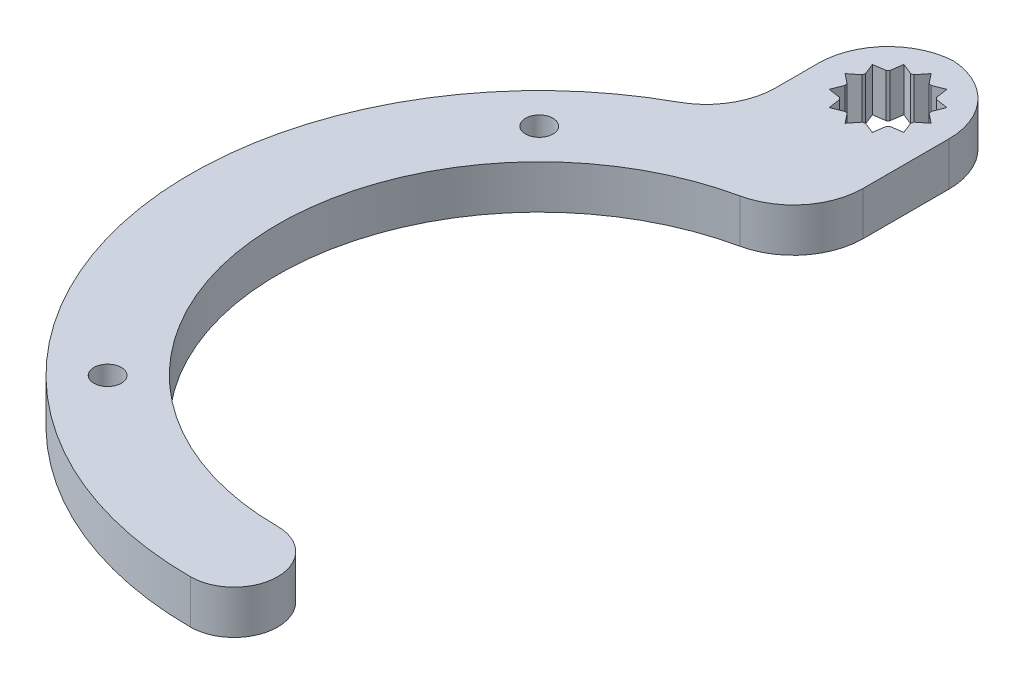
SolidWorks part; units mm, degrees
material "Pine"
ref_plane "Front Plane" through (0, 0, 0) normal (0, 0, 1) x (1, 0, 0)
ref_plane "Top Plane" through (0, 0, 0) normal (0, 1, 0) x (1, 0, 0)
ref_plane "Right Plane" through (0, 0, 0) normal (1, 0, 0) x (0, 0, -1)
sketch "Sketch1" plane through (0, 0, 0) normal (0, 1, 0) x (1, 0, 0)
  line L0 (0, 0) -> (19.05, 0)
  line L1 (19.05, 0) -> (19.05, -19.05)
  line L2 (0, 0) -> (0, -22.7571)
  line L3 (19.05, -19.05) -> (19.05, -120.65) construction
  line L4 (19.05, -31.75) -> (19.05, -19.05)
  line L5 (19.05, -9.525) -> (0, -9.525) construction
  line L6 (19.05, -69.85) -> (-12.3809, -38.4191) construction
  line L7 (19.05, -69.85) -> (-12.3809, -101.2809) construction
  arc A0 (19.05, -19.05) -> (19.05, -120.65) centre (19.05, -69.85) ccw
  arc A1 (19.05, -31.75) -> (19.05, -107.95) centre (19.05, -69.85) ccw
  arc A2 (19.05, -107.95) -> (19.05, -120.65) centre (19.05, -114.3) cw
  circle A3 centre (9.525, -9.525) radius 3
  circle A4 centre (19.05, -69.85) radius 44.45 construction
  circle A5 centre (-12.3809, -38.4191) radius 2
  circle A6 centre (-12.3809, -101.2809) radius 2
  dimension "D2" = 76.2
  dimension "D5" = 6
  dimension "D6" = 88.9
  dimension "D7" = 4
  dimension "D8" = 4
  dimension "D1" = 12.7
  dimension "D3" = 19.05
  dimension "D4" = 19.05
  dimension "D9" = 135
  dimension "D10" = 45
extrude "Boss-Extrude1" add sketch "Sketch1" along normal blind 6.35 contours L3 A1 L4 A0 | A0 L1 L0 L2 | A2 L3 region at (9.525, 0, 0.2968) region at (9.569, 0, 21.1296)
fillet "Fillet1" radius 10.16 4 edges at (0, 3.175, 22.7571) (19.05, 3.175, 31.75) (0, 3.175, 0) (19.05, 3.175, 0)
sketch "Sketch2" plane through (0, 6.35, 0) normal (0, 1, 0) x (1, 0, 0)
  line L0 (9.525, -4.525) -> (9.525, -3.255) construction
  line L1 (9.525, -3.255) -> (10.6293, -4.6485)
  line L2 (9.525, -3.255) -> (8.4207, -4.6485)
  line L3 (12.66, -4.095) -> (11.0069, -4.7496)
  line L4 (12.66, -4.095) -> (12.9196, -5.854)
  line L5 (12.025, -5.1949) -> (12.66, -4.095) construction
  line L6 (14.955, -6.39) -> (13.196, -6.1304)
  line L7 (14.955, -6.39) -> (14.3004, -8.0431)
  line L8 (13.8551, -7.025) -> (14.955, -6.39) construction
  line L9 (15.795, -9.525) -> (14.4015, -8.4207)
  line L10 (15.795, -9.525) -> (14.4015, -10.6293)
  line L11 (14.525, -9.525) -> (15.795, -9.525) construction
  line L12 (14.955, -12.66) -> (14.3004, -11.0069)
  line L13 (14.955, -12.66) -> (13.196, -12.9196)
  line L14 (13.8551, -12.025) -> (14.955, -12.66) construction
  line L15 (12.66, -14.955) -> (12.9196, -13.196)
  line L16 (12.66, -14.955) -> (11.0069, -14.3004)
  line L17 (12.025, -13.8551) -> (12.66, -14.955) construction
  line L18 (9.525, -15.795) -> (10.6293, -14.4015)
  line L19 (9.525, -15.795) -> (8.4207, -14.4015)
  line L20 (9.525, -14.525) -> (9.525, -15.795) construction
  line L21 (6.39, -14.955) -> (8.0431, -14.3004)
  line L22 (6.39, -14.955) -> (6.1304, -13.196)
  line L23 (7.025, -13.8551) -> (6.39, -14.955) construction
  line L24 (4.095, -12.66) -> (5.854, -12.9196)
  line L25 (4.095, -12.66) -> (4.7496, -11.0069)
  line L26 (5.1949, -12.025) -> (4.095, -12.66) construction
  line L27 (3.255, -9.525) -> (4.6485, -10.6293)
  line L28 (3.255, -9.525) -> (4.6485, -8.4207)
  line L29 (4.525, -9.525) -> (3.255, -9.525) construction
  line L31 (4.095, -6.39) -> (4.7496, -8.0431)
  line L33 (4.095, -6.39) -> (5.854, -6.1304)
  line L35 (5.1949, -7.025) -> (4.095, -6.39) construction
  line L37 (6.39, -4.095) -> (6.1304, -5.854)
  line L39 (6.39, -4.095) -> (8.0431, -4.7496)
  line L41 (7.025, -5.1949) -> (6.39, -4.095) construction
  arc A0 (6.1304, -5.854) -> (5.854, -6.1304) centre (9.525, -9.525) ccw construction
  arc A1 (6.1304, -5.854) -> (5.854, -6.1304) centre (9.525, -9.525) ccw
  arc A2 (4.7496, -8.0431) -> (4.6485, -8.4207) centre (9.525, -9.525) ccw construction
  arc A3 (4.7496, -8.0431) -> (4.6485, -8.4207) centre (9.525, -9.525) ccw
  arc A4 (4.6485, -10.6293) -> (4.7496, -11.0069) centre (9.525, -9.525) ccw construction
  arc A5 (4.6485, -10.6293) -> (4.7496, -11.0069) centre (9.525, -9.525) ccw
  arc A6 (5.854, -12.9196) -> (6.1304, -13.196) centre (9.525, -9.525) ccw construction
  arc A7 (5.854, -12.9196) -> (6.1304, -13.196) centre (9.525, -9.525) ccw
  arc A8 (8.0431, -14.3004) -> (8.4207, -14.4015) centre (9.525, -9.525) ccw construction
  arc A9 (8.0431, -14.3004) -> (8.4207, -14.4015) centre (9.525, -9.525) ccw
  arc A10 (10.6293, -14.4015) -> (11.0069, -14.3004) centre (9.525, -9.525) ccw construction
  arc A11 (10.6293, -14.4015) -> (11.0069, -14.3004) centre (9.525, -9.525) ccw
  arc A12 (12.9196, -13.196) -> (13.196, -12.9196) centre (9.525, -9.525) ccw construction
  arc A13 (12.9196, -13.196) -> (13.196, -12.9196) centre (9.525, -9.525) ccw
  arc A14 (14.3004, -11.0069) -> (14.4015, -10.6293) centre (9.525, -9.525) ccw construction
  arc A15 (14.3004, -11.0069) -> (14.4015, -10.6293) centre (9.525, -9.525) ccw
  arc A16 (14.4015, -8.4207) -> (14.3004, -8.0431) centre (9.525, -9.525) ccw construction
  arc A17 (14.4015, -8.4207) -> (14.3004, -8.0431) centre (9.525, -9.525) ccw
  arc A18 (13.196, -6.1304) -> (12.9196, -5.854) centre (9.525, -9.525) ccw construction
  arc A19 (13.196, -6.1304) -> (12.9196, -5.854) centre (9.525, -9.525) ccw
  arc A20 (11.0069, -4.7496) -> (10.6293, -4.6485) centre (9.525, -9.525) ccw construction
  arc A21 (11.0069, -4.7496) -> (10.6293, -4.6485) centre (9.525, -9.525) ccw
  arc A22 (8.4207, -4.6485) -> (8.0431, -4.7496) centre (9.525, -9.525) ccw construction
  arc A23 (8.4207, -4.6485) -> (8.0431, -4.7496) centre (9.525, -9.525) ccw
  point P52 (9.525, -9.525)
  dimension "D1" = 10
  dimension "D3" = 1.778
  dimension "D2" = 1.27
extrude "Cut-Extrude1" cut sketch "Sketch2" against normal through all
equation "\"D6@Sketch1\" = \"D2@Sketch1\" + \"D1@Sketch1\""
